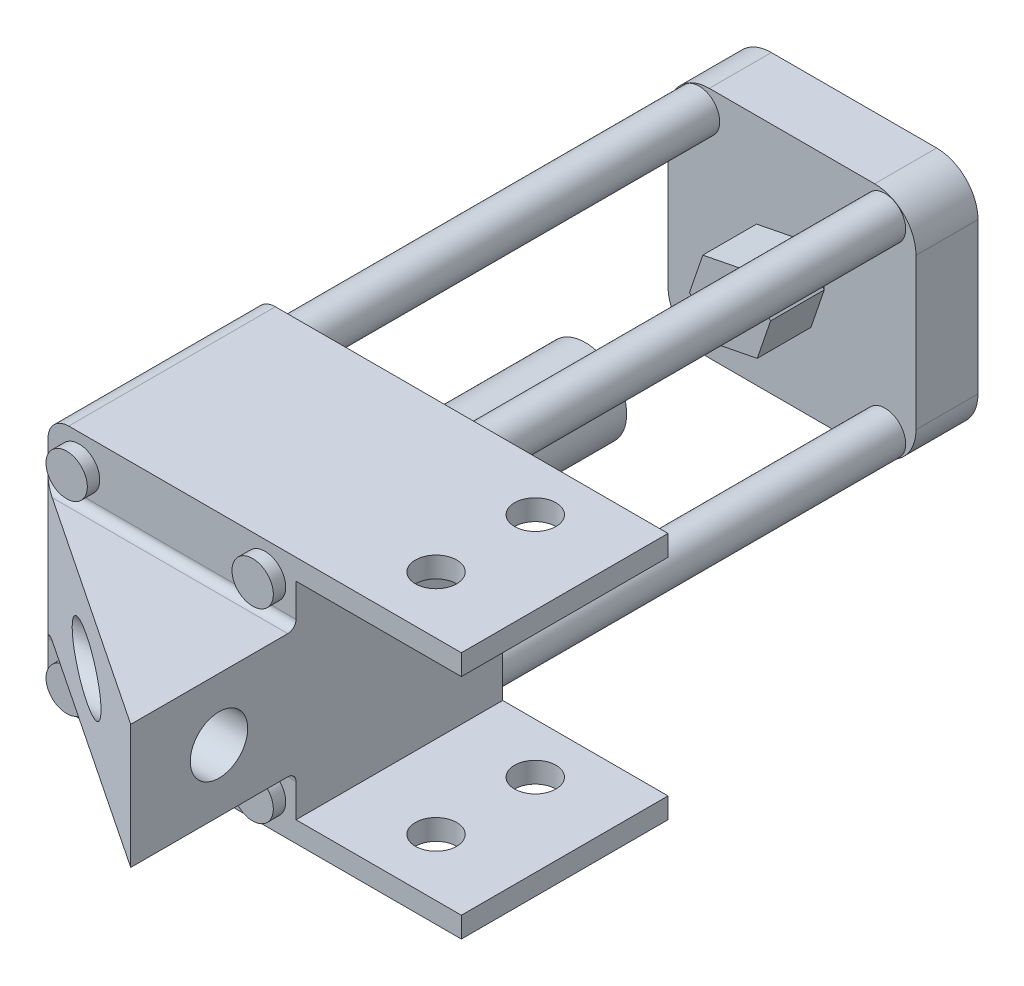
SolidWorks part; units mm, degrees
ref_plane "Ön Düzlem" through (0, 0, 0) normal (0, 0, 1) x (1, 0, 0)
ref_plane "Üst Düzlem" through (0, 0, 0) normal (0, 1, 0) x (1, 0, 0)
ref_plane "Sağ Düzlem" through (0, 0, 0) normal (1, 0, 0) x (0, 0, -1)
sketch "Çizim1" plane through (0, 0, 0) normal (0, 0, 1) x (1, 0, 0)
  line L1 (30, 30) -> (-30, 30)
  line L2 (30, 30) -> (30, -30)
  line L3 (30, -30) -> (-30, -30)
  line L4 (-30, 30) -> (-30, -30)
  line L5 (30, 30) -> (-30, -30) construction
  line L6 (30, -30) -> (-30, 30) construction
  point P0 (0, 0)
  dimension "D1" = 60
  dimension "D2" = 60
extrude "Yükseklik-Ekstrüzyon1" add sketch "Çizim1" along normal blind 50
sketch "Çizim2" plane through (0, 0, 0) normal (0, 0, -1) x (-1, 0, 0)
  circle A0 centre (0, 0) radius 10
extrude "Yükseklik-Ekstrüzyon2" add sketch "Çizim2" along normal blind 50
sketch "Çizim3" plane through (0, 0, -50) normal (0, 0, -1) x (-1, 0, 0)
  circle A0 centre (0, 0) radius 4.4827
extrude "Yükseklik-Ekstrüzyon3" add sketch "Çizim3" along normal blind 35
sketch "Çizim4" plane through (0, 0, -85) normal (0, 0, -1) x (-1, 0, 0)
  line L1 (9.8102, -1.9392) -> (6.5845, 7.5262)
  line L2 (6.5845, 7.5262) -> (-3.2257, 9.4655)
  line L3 (-3.2257, 9.4655) -> (-9.8102, 1.9392)
  line L4 (-9.8102, 1.9392) -> (-6.5845, -7.5262)
  line L5 (-6.5845, -7.5262) -> (3.2257, -9.4655)
  line L6 (3.2257, -9.4655) -> (9.8102, -1.9392)
  circle A0 centre (0, 0) radius 8.6603 construction
extrude "Yükseklik-Ekstrüzyon4" add sketch "Çizim4" along normal blind 15
chamfer "Pah1" distance 2 angle 45 6 edges at (1.6794, -8.4959, -100) (8.1973, -2.7935, -100) (6.5179, 5.7023, -100) (-1.6794, 8.4959, -100) (-8.1973, 2.7935, -100) (-6.5179, -5.7023, -100)
sketch "Çizim5" plane through (0, 0, 0) normal (0, 0, -1) x (-1, 0, 0)
  point P0 (0, 0)
sketch "Çizim8" plane through (0, 0, 0) normal (0, 0, -1) x (-1, 0, 0)
  line L5 (22.5, 22.5) -> (-22.5, -22.5) construction
  line L6 (22.5, -22.5) -> (-22.5, 22.5) construction
  circle A0 centre (-22.5, 22.5) radius 5
  circle A1 centre (22.5, 22.5) radius 5
  circle A2 centre (22.5, -22.5) radius 5
  circle A3 centre (-22.5, -22.5) radius 5
  point P0 (0, 0)
  dimension "D1" = 45
  dimension "D2" = 45
extrude "Yükseklik-Ekstrüzyon7" add sketch "Çizim8" along normal blind 100 and the other way blind 53
sketch "Çizim9" plane through (0, 0, -100) normal (0, 0, -1) x (-1, 0, 0)
  line L0 (-30, -30) -> (-30, 30) construction
  line L1 (30, 28.2627) -> (-30, 28.2627)
  line L2 (30, 28.2627) -> (30, -28.2627)
  line L3 (30, -28.2627) -> (-30, -28.2627)
  line L4 (-30, 28.2627) -> (-30, -28.2627)
  line L5 (30, 28.2627) -> (-30, -28.2627) construction
  line L6 (30, -28.2627) -> (-30, 28.2627) construction
  point P0 (0, 0)
extrude "Yükseklik-Ekstrüzyon8" add sketch "Çizim9" along normal blind 15
fillet "Radyus2" radius 10 4 edges at (30, -28.2627, -107.5) (30, 28.2627, -107.5) (-30, -28.2627, -107.5) (-30, 28.2627, -107.5)
sketch "Çizim10" plane through (0, 0, 0) normal (0, 1, 0) x (1, 0, 0)
  line L0 (30, -50) -> (30, -90)
  line L1 (30, -90) -> (-30, -50)
  line L2 (-30, -50) -> (30, -50)
extrude "Yükseklik-Ekstrüzyon9" add sketch "Çizim10" along normal blind 15 and the other way blind 15
sketch "Çizim11" plane through (30, 0, 0) normal (1, 0, 0) x (0, 0, -1)
  circle A0 centre (-68.6446, 0) radius 6.9539
extrude "Kes-Ekstrüzyon1" cut sketch "Çizim11" against normal blind 75
fillet "Radyus3" radius 5 4 edges at (30, 30, 25) (30, -30, 25) (-30, 30, 25) (-30, -30, 25)
sketch "Çizim12" plane through (0, -30, 0) normal (0, -1, 0) x (1, 0, 0)
  line L1 (25, 0) -> (70, 0)
  line L2 (25, 0) -> (25, 50)
  line L3 (25, 50) -> (70, 50)
  line L4 (70, 0) -> (70, 50)
  dimension "D1" = 45
extrude "Yükseklik-Ekstrüzyon10" add sketch "Çizim12" against normal blind 5
sketch "Çizim13" plane through (0, 30, 0) normal (0, 1, 0) x (1, 0, 0)
  line L1 (70, 0) -> (25, 0)
  line L2 (70, 0) -> (70, -50)
  line L3 (70, -50) -> (25, -50)
  line L4 (25, 0) -> (25, -50)
extrude "Yükseklik-Ekstrüzyon11" add sketch "Çizim13" against normal blind 5
sketch "Çizim14" plane through (0, 30, 0) normal (0, 1, 0) x (1, 0, 0)
  line L0 (70, -50) -> (70, 0) construction
  circle A0 centre (50, -12.1238) radius 5
  circle A1 centre (50, -36.1238) radius 5
  dimension "D1" = 20
  dimension "D2" = 20
  dimension "D3" = 24
extrude "Kes-Ekstrüzyon2" cut sketch "Çizim14" against normal blind 98
fillet "Radyus4" radius 2 2 edges at (0, 15, 50) (0, -15, 50)
